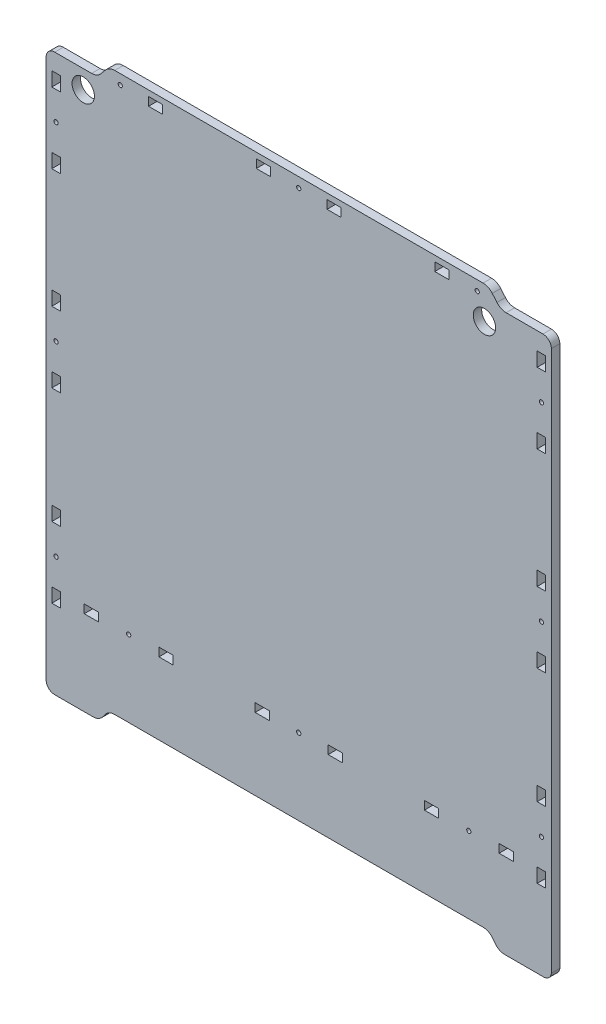
SolidWorks part; units mm, degrees
ref_plane "Спереди" through (0, 0, 0) normal (0, 0, 1) x (1, 0, 0)
ref_plane "Сверху" through (0, 0, 0) normal (0, 1, 0) x (1, 0, 0)
ref_plane "Справа" through (0, 0, 0) normal (1, 0, 0) x (0, 0, -1)
sketch "Эскиз1" plane through (0, 0, 0) normal (0, 0, 1) x (1, 0, 0)
  line L0 (146.8614, 191.5323) -> (172.8978, 191.5323)
  line L1 (-168.1958, 44.9723) -> (-168.1958, 34.9723)
  line L2 (174.8042, 34.9723) -> (168.8042, 34.9723)
  line L3 (178.8042, 185.543) -> (178.8042, -196.6758)
  line L4 (-178.1958, 185.543) -> (-178.1958, -195.7677)
  line L5 (172.8978, -201.7677) -> (145.8614, -201.7677)
  line L6 (-138.5545, -198.7314) -> (-136.2586, -195.7117)
  line L7 (-172.1022, -201.7677) -> (-145.0658, -201.7677)
  line L8 (-129.7473, -192.6754) -> (130.5428, -192.6754)
  line L9 (139.35, -198.7314) -> (137.0542, -195.7117)
  line L10 (174.8042, 179.1323) -> (174.8042, 169.359)
  line L11 (96.4442, 197.5323) -> (106.4199, 197.5323)
  line L12 (106.4199, 197.5323) -> (106.4442, 197.5149)
  line L13 (174.8042, 169.359) -> (174.8042, 169.1323)
  line L14 (137.0542, 198.496) -> (140.35, 194.5682)
  line L15 (130.5428, 201.5323) -> (-129.7473, 201.5323)
  line L16 (-136.2586, 198.4964) -> (-139.5545, 194.5686)
  line L17 (-146.0658, 191.5323) -> (-172.1022, 191.5323)
  line L18 (106.4199, 191.5323) -> (96.4442, 191.5323)
  line L19 (-168.1958, 34.9723) -> (-174.1958, 34.9723)
  line L20 (31.0942, -141.7677) -> (21.0942, -141.7677)
  line L21 (168.8042, 34.9723) -> (168.8042, 44.9723)
  line L22 (31.0942, -135.7677) -> (31.0942, -141.7677)
  line L23 (-30.4858, -135.7677) -> (-20.4858, -135.7677)
  line L24 (21.0942, -141.7677) -> (21.0942, -135.7677)
  line L25 (-20.4858, -141.7677) -> (-30.4858, -141.7677)
  line L26 (-20.4858, -135.7677) -> (-20.4858, -141.7677)
  line L27 (-168.1958, 179.1323) -> (-168.1958, 169.1323)
  line L28 (-30.4858, -141.7677) -> (-30.4858, -135.7677)
  line L29 (-174.1958, 34.9723) -> (-174.1958, 44.9723)
  line L30 (-174.1958, 44.9723) -> (-168.1958, 44.9723)
  line L31 (21.0942, -135.7677) -> (31.0942, -135.7677)
  line L32 (-174.1958, 179.1323) -> (-168.1958, 179.1323)
  line L33 (99.0942, -141.7677) -> (89.0942, -141.7677)
  line L34 (89.0942, -141.7677) -> (89.0942, -135.7677)
  line L35 (89.0942, -135.7677) -> (99.0942, -135.7677)
  line L36 (99.0942, -135.7677) -> (99.0942, -141.7677)
  line L37 (151.8942, -141.7677) -> (141.8942, -141.7677)
  line L38 (141.8942, -141.7677) -> (141.8942, -135.7677)
  line L39 (141.8942, -135.7677) -> (151.8942, -135.7677)
  line L40 (151.8942, -135.7677) -> (151.8942, -141.7677)
  line L41 (-19.6852, 191.5323) -> (-29.6852, 191.5323)
  line L42 (-29.6852, 191.5323) -> (-29.6864, 197.5323)
  line L43 (-29.6864, 197.5323) -> (-19.6864, 197.5323)
  line L44 (-19.6864, 197.5323) -> (-19.6852, 191.5323)
  line L45 (-174.1958, 119.1323) -> (-174.1958, 129.1323)
  line L46 (-141.2858, -135.7677) -> (-141.2858, -141.7677)
  line L47 (-151.2858, -135.7677) -> (-141.2858, -135.7677)
  line L48 (20.2942, 197.5323) -> (30.2942, 197.5323)
  line L49 (30.2942, 197.5323) -> (30.2942, 191.5323)
  line L50 (-141.2858, -141.7677) -> (-151.2858, -141.7677)
  line L51 (-174.1958, -5.0277) -> (-168.1958, -5.0277)
  line L52 (-174.1958, -15.0277) -> (-174.1958, -5.0277)
  line L53 (-174.1958, 169.1323) -> (-174.1958, 179.1323)
  line L54 (-168.1958, -5.0277) -> (-168.1958, -15.0277)
  line L55 (30.2942, 191.5323) -> (20.2942, 191.5323)
  line L56 (-151.2858, -141.7677) -> (-151.2858, -135.7677)
  line L57 (-168.1958, 119.1323) -> (-174.1958, 119.1323)
  line L58 (-168.1958, -15.0277) -> (-174.1958, -15.0277)
  line L59 (20.2942, 191.5323) -> (20.2942, 197.5323)
  line L60 (-168.1958, 169.1323) -> (-174.1958, 169.1323)
  line L61 (-174.1958, -86.7577) -> (-168.1958, -86.7577)
  line L62 (-174.1958, -96.7577) -> (-174.1958, -86.7577)
  line L63 (-168.1958, 129.1323) -> (-168.1958, 119.1323)
  line L64 (-174.1958, 129.1323) -> (-168.1958, 129.1323)
  line L65 (-174.1958, -136.7477) -> (-168.1958, -136.7477)
  line L66 (-174.1958, -146.7477) -> (-174.1958, -136.7477)
  line L67 (-98.4858, -141.7677) -> (-98.4858, -135.7677)
  line L68 (-98.4858, -135.7677) -> (-88.4858, -135.7677)
  line L69 (-88.4858, -135.7677) -> (-88.4858, -141.7677)
  line L70 (-168.1958, -146.7477) -> (-174.1958, -146.7477)
  line L71 (-168.1958, -136.7477) -> (-168.1958, -146.7477)
  line L72 (-168.1958, -96.7577) -> (-174.1958, -96.7577)
  line L73 (-168.1958, -86.7577) -> (-168.1958, -96.7577)
  line L74 (174.8042, -15.0277) -> (168.8042, -15.0277)
  line L75 (168.8042, -96.7577) -> (168.8042, -86.7577)
  line L76 (174.8042, -5.0277) -> (174.8042, -15.0277)
  line L77 (174.8042, -86.7577) -> (174.8042, -96.7577)
  line L78 (174.8042, -96.7577) -> (168.8042, -96.7577)
  line L79 (168.8042, -146.7477) -> (168.8042, -136.7477)
  line L80 (168.8042, -136.7477) -> (174.8042, -136.7477)
  line L81 (174.8042, -136.7477) -> (174.8042, -146.7477)
  line L82 (168.8042, -86.7577) -> (174.8042, -86.7577)
  line L83 (168.8042, 179.1323) -> (174.8042, 179.1323)
  line L84 (168.8042, 119.1323) -> (168.8042, 129.1323)
  line L85 (168.8042, 129.1323) -> (174.8042, 129.1323)
  line L86 (174.8042, 129.1323) -> (174.8042, 119.1323)
  line L87 (168.8042, 44.9723) -> (174.8042, 44.9723)
  line L88 (174.8042, 169.1323) -> (168.8042, 169.1323)
  line L89 (174.8042, 44.9723) -> (174.8042, 34.9723)
  line L90 (-95.8352, 191.5323) -> (-105.8352, 191.5323)
  line L91 (106.4442, 191.3325) -> (106.4199, 191.5323)
  line L92 (-105.8352, 191.5323) -> (-105.8364, 197.5323)
  line L93 (174.8042, 119.1323) -> (168.8042, 119.1323)
  line L94 (-105.8364, 197.5323) -> (-95.8364, 197.5323)
  line L95 (-95.8364, 197.5323) -> (-95.8352, 191.5323)
  line L96 (174.8042, -146.7477) -> (168.8042, -146.7477)
  line L97 (168.8042, 169.1323) -> (168.8042, 179.1323)
  line L98 (106.4442, 197.5149) -> (106.4442, 191.3325)
  line L99 (-88.4858, -141.7677) -> (-98.4858, -141.7677)
  line L100 (96.4442, 191.5323) -> (96.4442, 197.5323)
  line L101 (168.8042, -15.0277) -> (168.8042, -5.0277)
  line L102 (168.8042, -5.0277) -> (174.8042, -5.0277)
  line L103 (-158.5792, -141.7677) -> (201.8861, -141.7677) construction
  arc A0 (-172.1022, 191.5323) -> (-178.1958, 185.543) centre (-172.1958, 185.5331) ccw
  circle A1 centre (120.4942, -138.7677) radius 1.5
  circle A2 centre (0.3042, -138.7677) radius 1.5
  circle A3 centre (-119.8858, -138.7677) radius 1.5
  arc A4 (172.8978, -201.7677) -> (178.8042, -196.6758) centre (173.2588, -196.2149) ccw
  arc A5 (-129.7473, -192.6754) -> (-136.2586, -195.7117) centre (-129.7473, -201.1754) ccw
  arc A6 (139.35, -198.7314) -> (145.8614, -201.7677) centre (145.8614, -193.2677) ccw
  arc A7 (-145.0658, -201.7677) -> (-138.5545, -198.7314) centre (-145.0658, -193.2677) ccw
  arc A8 (-178.1958, -195.7677) -> (-172.1022, -201.7677) centre (-172.1958, -195.7684) ccw
  arc A9 (137.0542, -195.7117) -> (130.5428, -192.6754) centre (130.5428, -201.1754) ccw
  arc A10 (178.8042, 185.543) -> (172.8978, 191.5323) centre (172.8042, 185.5331) ccw
  arc A11 (137.0542, 198.496) -> (130.5428, 201.5323) centre (130.5428, 193.0323) ccw
  arc A12 (140.35, 194.5682) -> (146.8614, 191.5323) centre (146.861, 200.0323) ccw
  circle A13 centre (-171.1958, -116.7377) radius 1.5
  circle A14 centre (-171.1958, 14.9723) radius 1.5
  circle A15 centre (171.8042, 149.1323) radius 1.5
  circle A16 centre (126.4442, 194.5323) radius 1.5
  circle A17 centre (-151.9958, 178.5323) radius 7.9
  circle A18 centre (171.8042, -116.7377) radius 1.5
  circle A19 centre (171.8042, 14.9723) radius 1.5
  circle A20 centre (-171.1958, 149.1323) radius 1.5
  circle A21 centre (-125.8358, 194.5323) radius 1.5
  circle A22 centre (0.3042, 194.5444) radius 1.5
  circle A23 centre (131.5042, 178.5323) radius 7.9
  arc A24 (-129.7473, 201.5323) -> (-136.2586, 198.4964) centre (-129.7476, 193.0323) ccw
  arc A25 (-146.0658, 191.5323) -> (-139.5545, 194.5686) centre (-146.0658, 200.0323) ccw
  point P155 (-174.1958, 124.1323)
  point P156 (-171.1958, -146.7477)
  point P157 (106.4442, 194.4237)
  point P161 (31.0942, -138.7677)
  dimension "D1" = 357
  dimension "D2" = 403.3
  dimension "D3" = 403.3
  dimension "D4" = 23
  dimension "D5" = 26.2
  dimension "D6" = 4
  dimension "D7" = 10
  dimension "D8" = 22.4
  dimension "D9" = 10
  dimension "D10" = 7
  dimension "D11" = 20
  dimension "D12" = 20
  dimension "D13" = 10
  dimension "D14" = 74.16
  dimension "D15" = 4
  dimension "D16" = 6
  dimension "D17" = 6
  dimension "D18" = 10
  dimension "D19" = 4
  dimension "D20" = 20
  dimension "D21" = 20
  dimension "D22" = 10
  dimension "D23" = 7
  dimension "D24" = 4
  dimension "D25" = 71.73
  dimension "D26" = 4
  dimension "D27" = 10
  dimension "D28" = 19.98
  dimension "D29" = 7
  dimension "D30" = 20.01
  dimension "D31" = 10
  dimension "D32" = 55.02
  dimension "D33" = 4
  dimension "D34" = 23
  dimension "D35" = 47.3
  dimension "D36" = 10
  dimension "D37" = 12.4
  dimension "D38" = 10
  dimension "D39" = 20
  dimension "D40" = 20
  dimension "D41" = 10
  dimension "D42" = 74.16
  dimension "D43" = 10
  dimension "D44" = 6
  dimension "D45" = 6
  dimension "D46" = 6
  dimension "D47" = 6
  dimension "D48" = 6
  dimension "D49" = 4
  dimension "D50" = 7
  dimension "D51" = 4
  dimension "D52" = 6
  dimension "D53" = 6
  dimension "D54" = 4
  dimension "D55" = 20
  dimension "D56" = 20
  dimension "D57" = 7
  dimension "D58" = 4
  dimension "D59" = 6
  dimension "D60" = 71.73
  dimension "D61" = 4
  dimension "D62" = 6
  dimension "D63" = 7
  dimension "D64" = 19.98
  dimension "D65" = 20.01
  dimension "D66" = 10
  dimension "D67" = 6
  dimension "D68" = 4
  dimension "D69" = 55.02
  dimension "D70" = 7
  dimension "D71" = 4
  dimension "D72" = 4
  dimension "D73" = 4
  dimension "D74" = 7
  dimension "D75" = 4
  dimension "D76" = 6
  dimension "D77" = 10
  dimension "D78" = 6
  dimension "D79" = 10
  dimension "D80" = 10
  dimension "D81" = 6
  dimension "D82" = 6
  dimension "D83" = 10
  dimension "D84" = 52.36
  dimension "D85" = 20
  dimension "D86" = 66.15
  dimension "D87" = 178.5
  dimension "D88" = 19.99
  dimension "D89" = 52.36
  dimension "D90" = 20
  dimension "D91" = 66.15
  dimension "D92" = 19.99
  dimension "D93" = 6
  dimension "D94" = 10
  dimension "D95" = 3
  dimension "D96" = 6
  dimension "D97" = 10
  dimension "D98" = 16.91
  dimension "D99" = 21.4
  dimension "D100" = 21.4
  dimension "D101" = 6
  dimension "D102" = 10
  dimension "D103" = 58
  dimension "D104" = 6
  dimension "D105" = 60
  dimension "D106" = 10
  dimension "D107" = 3
  dimension "D108" = 6
  dimension "D109" = 10
  dimension "D110" = 58
  dimension "D111" = 16.91
  dimension "D112" = 10
  dimension "D113" = 6
  dimension "D114" = 3
  dimension "D115" = 21.4
  dimension "D116" = 21.4
  dimension "D117" = 178.5
  dimension "D118" = 178.5
extrude "Бобышка-Вытянуть1" add sketch "Эскиз1" along normal blind 6
